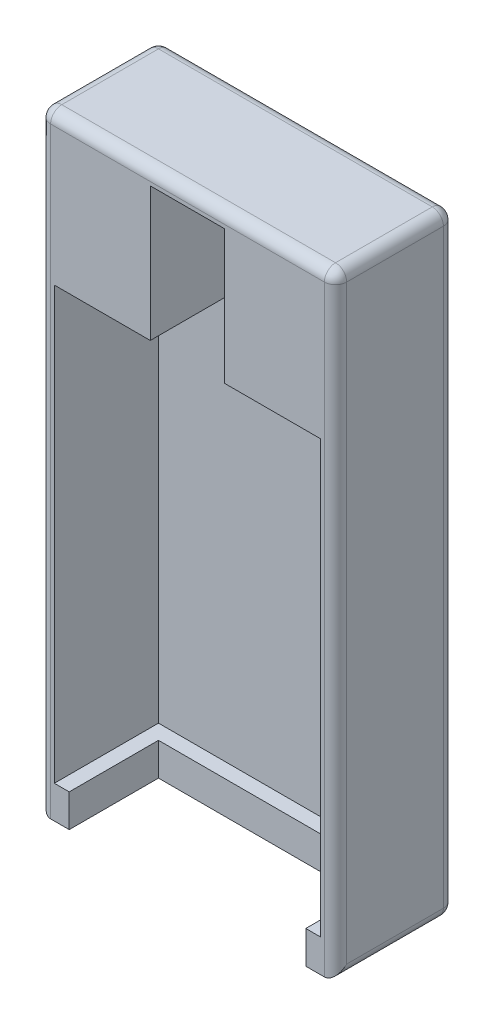
SolidWorks part; units mm, degrees
ref_plane "Front Plane" through (0, 0, 0) normal (0, 0, 1) x (1, 0, 0)
ref_plane "Top Plane" through (0, 0, 0) normal (0, 1, 0) x (1, 0, 0)
ref_plane "Right Plane" through (0, 0, 0) normal (1, 0, 0) x (0, 0, -1)
sketch "Sketch1" plane through (0, 0, 0) normal (0, 1, 0) x (1, 0, 0)
  line L0 (-22.733, -7.62) -> (-22.733, -10.16)
  line L1 (-25.273, -10.16) -> (25.273, -10.16)
  line L2 (-25.273, -10.16) -> (-25.273, 10.16)
  line L3 (-25.273, 10.16) -> (25.273, 10.16)
  line L4 (25.273, -10.16) -> (25.273, 10.16)
  line L5 (-25.273, -10.16) -> (25.273, 10.16) construction
  line L6 (-25.273, 10.16) -> (25.273, -10.16) construction
  line L7 (-22.733, -7.62) -> (22.733, -7.62)
  line L8 (-22.733, -7.62) -> (-22.733, 7.62)
  line L9 (-22.733, 7.62) -> (22.733, 7.62)
  line L10 (22.733, -7.62) -> (22.733, 7.62)
  line L11 (-22.733, -7.62) -> (22.733, 7.62) construction
  line L12 (-22.733, 7.62) -> (22.733, -7.62) construction
  line L13 (22.733, -7.62) -> (22.733, -10.16)
  line L14 (-22.733, -7.62) -> (-25.273, -7.62) construction
  line L15 (-20.193, -5.08) -> (-20.193, -10.16)
  line L17 (-20.193, -5.08) -> (-20.193, 5.08)
  line L18 (-20.193, 5.08) -> (20.193, 5.08)
  line L19 (20.193, -5.08) -> (20.193, 5.08)
  line L20 (-20.193, -5.08) -> (20.193, 5.08) construction
  line L21 (-20.193, 5.08) -> (20.193, -5.08) construction
  line L22 (20.193, -5.08) -> (20.193, -10.16)
  line L23 (-20.193, -5.08) -> (-22.733, -5.08) construction
  line L24 (-20.193, 5.08) -> (-20.193, 7.62) construction
  line L25 (0, -3.175) -> (0, 3.81) construction
  line L26 (-6.35, -3.175) -> (-6.35, 3.81)
  line L27 (6.35, -3.175) -> (6.35, 3.81)
  line L28 (-6.35, -3.175) -> (-6.35, -10.16)
  line L29 (6.35, -3.175) -> (6.35, -10.16)
  arc A1 (6.35, 3.81) -> (-6.35, 3.81) centre (0, 3.81) ccw
  point P0 (0, 0)
  point P6 (0, 0)
  point P11 (0, 0)
  point P30 (0, 0)
  point P32 (0, 0)
  point P34 (0, 0)
  point P35 (0, 0)
  point P36 (0, 0)
  point P37 (0, -4.8165)
  point P38 (-6.35, -4.6973)
  point P39 (0, 0)
  point P40 (1.0112, 2.8921)
  dimension "D4" = 6.35
  dimension "D1" = 15.24
  dimension "D2" = 2.54
  dimension "D3" = 45.466
extrude "Boss-Extrude3" add sketch "Sketch1" along normal blind 5.588 contours A1 L3 L2 L1 L0 L8 L9 | A1 L9 L10 L13 L1 L4 L3 | L9 A1 | A1 L9 L8 L7 L15 L17 L18 | L15 L7 L0 L1 | L18 A1 L9 | A1 L18 L19 L22 L7 L10 L9 | L7 L22 L1 L13 region at (-21.463, 0, 8.89) region at (-22.4998, 0, 0) region at (-23.0573, 0, 8.89) region at (0, 0, -8.6557) region at (0, 0, -6.3086) region at (2.9848, 0, -9.7797) region at (13.9065, 0, -7.3868) region at (21.463, 0, 8.89)
extrude "Boss-Extrude4" add sketch "Sketch1<7>" along normal blind 73.66 from surface contours A1 L3 L2 L1 L0 L8 L9 | A1 L9 L10 L13 L1 L4 L3 | L9 A1 region at (-23.0573, 0, 8.89) region at (0, 0, -8.6557) region at (2.9848, 0, -9.7797) starting at face at (0, 5.588, 1.27)
sketch "Sketch1<7>" plane through (0, 0, 0) normal (0, 1, 0) x (1, 0, 0) same geometry as "Sketch1"
extrude "Boss-Extrude6" add sketch "Sketch1<8>" along normal blind 22.86 from surface contours A1 L3 L2 L1 L0 L8 L9 | A1 L9 L8 L7 L15 L17 L18 | A1 L18 L17 L15 L7 L28 L26 | L15 L7 L0 L1 | L28 L7 L15 L1 | A1 L9 L10 L13 L1 L4 L3 | A1 L18 L19 L22 L7 L10 L9 | A1 L27 L29 L7 L22 L19 L18 | L7 L29 L1 L22 | L7 L22 L1 L13 | L9 A1 region at (-21.463, 0, 8.89) region at (-22.4998, 0, 0) region at (-23.0573, 0, 8.89) region at (-13.2694, 0, 1.2681) region at (-13.2715, 0, 8.89) region at (0, 0, -8.6557) region at (13.2694, 0, 1.2681) region at (13.2715, 0, 8.89) region at (2.9848, 0, -9.7797) region at (13.9065, 0, -7.3868) region at (21.463, 0, 8.89) starting at face at (0, 79.248, 0.635)
sketch "Sketch1<8>" plane through (0, 0, 0) normal (0, 1, 0) x (1, 0, 0) same geometry as "Sketch1"
extrude "Boss-Extrude7" add sketch "Sketch1<9>" along normal blind 2.54 from surface contours L27 A1 L18 L26 L28 L7 L29 | L29 L7 L28 L1 | L18 A1 L9 | A1 L3 L2 L1 L0 L8 L9 | L15 L7 L0 L1 | A1 L9 L8 L7 L15 L17 L18 | L28 L7 L15 L1 | A1 L18 L17 L15 L7 L28 L26 | L9 A1 | A1 L18 L19 L22 L7 L10 L9 | A1 L9 L10 L13 L1 L4 L3 | A1 L27 L29 L7 L22 L19 L18 | L7 L29 L1 L22 | L7 L22 L1 L13 | L3 L4 L1 L2 region at (-21.463, 0, 8.89) region at (-22.4998, 0, 0) region at (-23.0573, 0, 8.89) region at (-13.2694, 0, 1.2681) region at (-13.2715, 0, 8.89) region at (0, 0, 1.274) region at (0, 0, 8.89) region at (0, 0, -8.6557) region at (0, 0, -6.3086) region at (13.2694, 0, 1.2681) region at (13.2715, 0, 8.89) region at (2.9848, 0, -9.7797) region at (13.9065, 0, -7.3868) region at (21.463, 0, 8.89) starting at face at (0, 102.108, -0.2746)
sketch "Sketch1<9>" plane through (0, 0, 0) normal (0, 1, 0) x (1, 0, 0) same geometry as "Sketch1"
fillet "Fillet1" radius 1.905 11 edges at (0, 0, -10.16) (-25.273, 52.324, -10.16) (-25.273, 52.324, 10.16) (-25.273, 0, 0) (25.273, 52.324, 10.16) (25.273, 52.324, -10.16) (25.273, 0, 0) (0, 104.648, -10.16) (25.273, 104.648, 0) (0, 104.648, 10.16) (-25.273, 104.648, 0)
